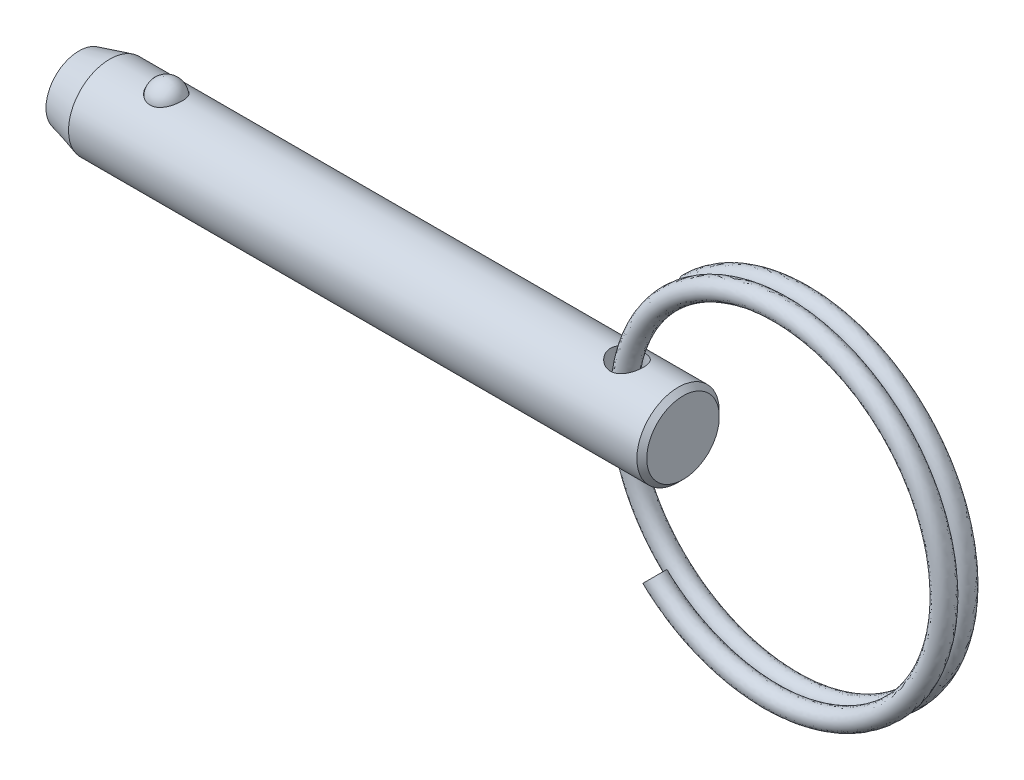
SolidWorks part; units mm, degrees
material "AISI 304"
ref_plane "Front" through (0, 0, 0) normal (0, 0, 1) x (1, 0, 0)
ref_plane "Top" through (0, 0, 0) normal (0, 1, 0) x (1, 0, 0)
ref_plane "Right" through (0, 0, 0) normal (1, 0, 0) x (0, 0, -1)
sketch "Sketch1" plane through (0, 0, 0) normal (0, 0, 1) x (1, 0, 0)
  line L0 (5.588, 2.794) -> (5.207, 3.175)
  line L1 (5.207, 3.175) -> (5.588, 3.175) construction
  line L4 (5.588, 2.794) -> (5.588, 0)
  line L5 (5.588, 3.175) -> (5.588, 2.794) construction
  line L16 (5.207, 3.175) -> (-38.5749, 3.175)
  line L17 (-40.9448, 3.175) -> (-40.9448, 2.54) construction
  line L19 (-38.5749, 3.175) -> (-40.9448, 3.175) construction
  line L22 (-40.9448, -3.175) -> (-38.5749, -3.175) construction
  line L23 (-34.2103, 2.8575) -> (-34.2103, -2.8575) construction
  line L24 (-40.9448, 0) -> (5.588, 0)
  line L27 (5.588, 0) -> (8.382, 0) construction
  line L29 (-40.9448, 0) -> (-40.9448, -2.54) construction
  line L36 (0, 0) -> (0, 3.175) construction
  line L37 (-40.9448, 2.54) -> (-40.9448, 0)
  line L38 (-38.5749, -3.175) -> (5.588, -3.175) construction
  line L39 (-40.9448, -2.54) -> (-40.9448, -3.175) construction
  line L40 (-38.5749, 3.175) -> (-40.9448, 2.54)
  line L42 (-38.5749, -3.175) -> (-40.9448, -2.54) construction
  line L43 (-38.5749, 3.175) -> (-38.5749, -3.175) construction
  circle A2 centre (-34.2103, 2.8575) radius 1.2319 construction
  point P35 (-33.02, 3.175)
  dimension "D2" = 5.715
  dimension "D11" = 0.9144
  dimension "A" = 6.35
  dimension "D" = 5.588
  dimension "E" = 7.2644
  dimension "D3" = 0.381
  dimension "Useable Length" = 33.02
  dimension "D12" = 5.08
  dimension "C" = 7.9248
  dimension "A1" = 15
revolve "Revolve1" add sketch "Sketch1" angle 360 about L27
sketch "Sketch2" plane through (0, 0, 0) normal (0, 0, 1) x (1, 0, 0)
  line L0 (-32.953, 2.8575) -> (-35.4676, 2.8575)
  line L1 (-34.2103, 4.0894) -> (-34.2103, 4.1148) construction
  line L2 (-32.953, 2.8575) -> (-30.4384, 2.8575) construction
  circle A0 centre (-34.2103, 2.8575) radius 1.2319 construction
  circle A1 centre (-34.2103, 2.8575) radius 1.2319 construction
  arc A2 (-35.4676, 2.8575) -> (-32.953, 2.8575) centre (-34.2103, 2.8575) cw
  dimension "D1" = 0.0254
revolve "Cut-Revolve1" cut sketch "Sketch2" angle 360 about L2
sketch "Sketch3" plane through (0, 0, 0) normal (0, 0, 1) x (1, 0, 0)
  line L0 (-32.9784, 2.8575) -> (-35.4422, 2.8575)
  line L1 (-32.9784, 2.8575) -> (-30.5146, 2.8575) construction
  circle A0 centre (-34.2103, 2.8575) radius 1.2319 construction
  arc A1 (-32.9784, 2.8575) -> (-35.4422, 2.8575) centre (-34.2103, 2.8575) ccw
revolve "Revolve2" add sketch "Sketch3" angle 360 about L1
sketch "Sketch4" plane through (0, 0, 0) normal (0, 0, 1) x (1, 0, 0)
  line L1 (1.27, -3.175) -> (2.54, -3.175)
  line L2 (1.27, -3.175) -> (1.27, 3.175)
  line L3 (1.27, 3.175) -> (2.54, 3.175)
  line L4 (2.54, -3.175) -> (2.54, 3.175)
  line L5 (1.27, -3.175) -> (1.27, -4.445) construction
  line L6 (2.54, 3.175) -> (5.588, 3.175) construction
  line L8 (0, -3.175) -> (0, 3.175) construction
  line L9 (0, 0) -> (1.27, 0) construction
  line L11 (1.27, 0) -> (2.54, 0) construction
  line L12 (5.207, 3.175) -> (-38.5749, 3.175) construction
  line L14 (-38.5749, -3.175) -> (5.588, -3.175) construction
  dimension "D1" = 2.54
revolve "Cut-Revolve2" cut sketch "Sketch4" angle 360 about L2
sketch "Sketch5" plane through (0, 0, 0) normal (0, 0, 1) x (1, 0, 0)
  line L0 (0, 0) -> (0.293, 0) construction
  line L1 (0.293, 0) -> (0.293, 3.175) construction
  line L2 (5.207, 3.175) -> (-38.5749, 3.175) construction
  line L3 (13.755, 0) -> (27.217, 0) construction
  line L4 (2.54, 3.175) -> (2.247, 3.175) construction
  line L5 (1.27, 3.175) -> (2.54, 3.175) construction
  line L6 (0.6728, 3.175) -> (0.6728, -3.175) construction
  line L7 (0.293, 3.175) -> (0, 3.175) construction
  line L8 (1.27, -3.175) -> (2.54, -3.175) construction
  line L9 (0.6728, -3.175) -> (2.54, -3.175) construction
  line L10 (0.293, 0) -> (13.755, 0) construction
  line L11 (13.755, 0) -> (8.7098, -10.8195) construction
  line L12 (2.247, 3.175) -> (0.6728, 3.175) construction
  line L13 (13.755, 11.938) -> (13.755, 13.462) construction
  line L14 (8.7098, -10.8195) -> (8.3878, -11.5101) construction
  circle A0 centre (13.755, 0) radius 13.462
  circle A1 centre (13.755, 0) radius 11.938 construction
  circle A2 centre (13.755, 0) radius 12.7 construction
  point P26 (13.755, 12.7)
  dimension "D1" = 65
  dimension "R Ring Dia" = 25.4
  dimension "Ring OD" = 1.524
curve "Helix/Spiral1" pitch 1.5494 height 1.3557 radius 13.462 left hand yes centre (13.755, 0, 0) axis (0, 0, -1) start towards (1, 0, 0)
sketch "Sketch6" plane through (114.0038, 0, 0) normal (0, 1, 0) x (0, 0, -1)
  line L0 (0, 112.1868) -> (0, 112.9488) construction
  line L1 (0, 112.9488) -> (0, 113.7108) construction
  circle A0 centre (0, 112.9488) radius 0.762
  dimension "D1" = 1.524
sketch "Sketch7" plane through (0, 0, 0) normal (0, 0, 1) x (1, 0, 0)
  circle A0 centre (13.755, 0) radius 13.462 construction
  circle A1 centre (13.755, 0) radius 13.462
curve "Helix/Spiral2" pitch 1.5494 height 1.3557 radius 13.462 left hand yes centre (13.755, 0, 0) axis (0, 0, 1) start towards (1, 0, 0)
sweep "Sweep1" add profiles "Sketch6" path "Helix/Spiral1"
sweep "Sweep2" add profiles "Sketch6<2>" path "Helix/Spiral2"
sketch "Sketch6<2>" plane through (114.0038, 0, 0) normal (0, 1, 0) x (0, 0, -1) same geometry as "Sketch6"
ref_plane "Plane1" through (0, -10.8195, 0) normal (0, 1, 0) x (-1, 0, 0)
sketch "Sketch8" plane through (0, -10.8195, 0) normal (0, 1, 0) x (-1, 0, 0)
  line L0 (143.6902, 0) -> (-8.7098, 0) construction
  line L1 (10.3402, -0.7779) -> (4.5066, -0.7779)
  line L2 (3.5004, -0.9415) -> (-7.2005, -4.517)
  line L3 (-7.2005, 4.517) -> (3.5004, 0.9415)
  line L4 (4.5066, 0.7779) -> (130.4738, 0.7779)
  line L5 (131.48, 0.9415) -> (142.1809, 4.517)
  line L6 (124.6402, -0.7779) -> (130.4738, -0.7779)
  line L7 (131.48, -0.9415) -> (142.1809, -4.517)
  line L8 (10.3402, -0.7779) -> (10.3402, 0.7779) construction
  arc A0 (-7.2005, 4.517) -> (-7.2005, -4.517) centre (-8.7098, 0) ccw
  arc A1 (142.1809, -4.517) -> (142.1809, 4.517) centre (143.6902, 0) ccw
  arc A2 (4.5066, -0.7779) -> (3.5004, -0.9415) centre (4.5066, -3.9529) ccw
  arc A3 (3.5004, 0.9415) -> (4.5066, 0.7779) centre (4.5066, 3.9529) ccw
  arc A4 (130.4738, -0.7779) -> (131.48, -0.9415) centre (130.4738, -3.9529) cw
  arc A5 (130.4738, 0.7779) -> (131.48, 0.9415) centre (130.4738, 3.9529) ccw
  point P6 (10.3402, 0)
  point P16 (3.9902, -0.7779)
  point P20 (3.9902, 0.7779)
  point P23 (130.9902, -0.7779)
  point P26 (130.9902, 0.7779)
  dimension "D2" = 4.7625
  dimension "D3" = 1.5557
  dimension "D6" = 3.175
  dimension "Lanyard Length" = 152.4
  dimension "D4" = 6.35
  dimension "D5" = 12.7
ref_plane "Plane2" through (-10.3402, 0, 0) normal (1, 0, 0) x (0, 0, -1)
sketch "Sketch9" plane through (-10.3402, 0, 0) normal (1, 0, 0) x (0, 0, -1)
  circle A0 centre (0.7779, -10.8195) radius 0.7779
sweep "Sweep3" [suppressed] add profiles "Sketch9" path "Sketch8"
sketch "Sketch10" [suppressed] plane through (-10.3402, 0, 0) normal (1, 0, 0) x (0, 0, -1)
  arc A0 (-0.3849, -10.1482) -> (-0.3849, -11.4908) centre (-0.7779, -10.8195) ccw
  circle A1 centre (0.7779, -10.8195) radius 0.7779
  arc A2 (0.3849, -11.4908) -> (0.3849, -10.1482) centre (0.7779, -10.8195) ccw
  arc A3 (-0.3849, -11.4908) -> (0.3849, -11.4908) centre (0, -12.1485) cw
  arc A4 (-0.3869, -9.3301) -> (-0.3869, -12.3089) centre (-0.7779, -10.8195) ccw
  arc A5 (0.3869, -12.3089) -> (0.3869, -9.3301) centre (0.7779, -10.8195) ccw
  circle A6 centre (-0.7779, -10.8195) radius 1.5399 construction
  circle A7 centre (-0.7779, -10.8195) radius 0.7779 construction
  arc A8 (-0.3849, -10.1482) -> (0.3849, -10.1482) centre (0, -9.4905) ccw
  arc A9 (-0.3869, -9.3301) -> (0.3869, -9.3301) centre (0, -7.856) ccw
  arc A10 (0.3869, -12.3089) -> (-0.3869, -12.3089) centre (0, -13.783) ccw
  point P4 (-0.034, -10.2746)
  point P8 (2.3178, -10.502)
  point P9 (0.762, -10.502)
  dimension "D3" = 1.524
  dimension "D4" = 0.762
  dimension "D2" = 0.762
  dimension "D1" = 0
extrude "Extrude1" [suppressed] add sketch "Sketch10" along normal blind 5.715 separate body
sketch "Sketch11" [suppressed] plane through (-124.6402, 0, 0) normal (1, 0, 0) x (0, 0, -1)
  arc A4 (-0.3849, -10.1482) -> (-0.3849, -11.4908) centre (-0.7779, -10.8195) ccw
  arc A5 (0.3849, -11.4908) -> (-0.3849, -11.4908) centre (0, -12.1485) ccw
  arc A6 (0.3849, -11.4908) -> (0.3849, -10.1482) centre (0.7779, -10.8195) ccw
  arc A7 (-0.3849, -10.1482) -> (0.3849, -10.1482) centre (0, -9.4905) ccw
  arc A8 (-0.3849, -10.1482) -> (-0.3849, -11.4908) centre (-0.7779, -10.8195) ccw
  arc A9 (0.3849, -11.4908) -> (-0.3849, -11.4908) centre (0, -12.1485) ccw
  arc A10 (0.3849, -11.4908) -> (0.3849, -10.1482) centre (0.7779, -10.8195) ccw
  arc A11 (-0.3849, -10.1482) -> (0.3849, -10.1482) centre (0, -9.4905) ccw
  arc A12 (-0.3869, -9.3301) -> (-0.3869, -12.3089) centre (-0.7779, -10.8195) ccw
  arc A13 (0.3869, -12.3089) -> (-0.3869, -12.3089) centre (0, -13.783) ccw
  arc A14 (0.3869, -12.3089) -> (0.3869, -9.3301) centre (0.7779, -10.8195) ccw
  arc A15 (-0.3869, -9.3301) -> (0.3869, -9.3301) centre (0, -7.856) ccw
  arc A16 (-0.3869, -9.3301) -> (-0.3869, -12.3089) centre (-0.7779, -10.8195) ccw
  arc A17 (0.3869, -12.3089) -> (-0.3869, -12.3089) centre (0, -13.783) ccw
  arc A18 (0.3869, -12.3089) -> (0.3869, -9.3301) centre (0.7779, -10.8195) ccw
  arc A19 (-0.3869, -9.3301) -> (0.3869, -9.3301) centre (0, -7.856) ccw
  dimension "D1" = 0
  dimension "D2" = 0
extrude "Extrude2" [suppressed] add sketch "Sketch11" against normal blind 5.715 separate body
sketch "Sketch12" plane through (0, -10.8195, 0) normal (0, 1, 0) x (-1, 0, 0)
  line L0 (174.4712, -5.2864) -> (168.9086, -5.2864) construction
  line L1 (174.4712, -5.9214) -> (158.1026, -5.9214)
  line L2 (174.4712, -5.9214) -> (174.4712, -4.6514)
  line L3 (174.4712, -4.6514) -> (158.3265, -4.6514)
  line L4 (158.1026, -5.9214) -> (158.3265, -4.6514) construction
  line L5 (158.1026, -5.9214) -> (142.7212, -0.3231)
  line L6 (168.9086, -5.2864) -> (158.2146, -5.2864) construction
  line L7 (158.3265, -4.6514) -> (143.1555, 0.8704)
  line L8 (142.7212, -0.3231) -> (143.1555, 0.8704)
  line L9 (158.2146, -5.2864) -> (148.1655, -1.6289) construction
  line L10 (148.1655, -1.6289) -> (142.9383, 0.2737) construction
  arc A0 (142.1809, -4.517) -> (142.1809, 4.517) centre (143.6902, 0) ccw construction
  dimension "D1" = 20
  dimension "D2" = 31.75
  dimension "D3" = 1.27
  dimension "D4" = 5.5626
extrude "Extrude3" [suppressed] add sketch "Sketch12" along normal mid plane 12.7 separate body
sketch "Sketch13" [suppressed] plane through (0, 0, -4.6514) normal (0, 0, 1) x (1, 0, 0)
  line L0 (-174.4712, -10.8195) -> (-158.3265, -10.8195) construction
  line L1 (-172.4782, -4.4695) -> (-174.4712, -4.4695)
  line L2 (-174.4712, -4.4695) -> (-158.3265, -4.4695) construction
  line L3 (-174.4712, -4.4695) -> (-176.4642, -4.4695)
  line L4 (-176.4642, -4.4695) -> (-176.4642, -17.1695)
  line L5 (-176.4642, -17.1695) -> (-174.4712, -17.1695)
  line L6 (-174.4712, -17.1695) -> (-172.4782, -17.1695)
  line L7 (-174.4712, -17.1695) -> (-158.3265, -17.1695) construction
  arc A0 (-172.4782, -4.4695) -> (-172.4782, -17.1695) centre (-163.3587, -10.8195) ccw
  circle A1 centre (-168.9086, -10.8195) radius 2.5781
  dimension "D1" = 5.1562
  dimension "D2" = 11.1125
extrude "Extrude4" [suppressed] cut sketch "Sketch13" against normal up to surface (1.27 mm away)
sketch "Sketch14" [suppressed] plane through (-17.0257, 0, 46.7778) normal (-0.342, 0, 0.9397) x (0.9397, 0, 0.342)
  line L3 (-136.2175, -4.4695) -> (-134.2245, -4.4695)
  line L4 (-134.2245, -4.4695) -> (-132.2315, -4.4695)
  line L5 (-132.2315, -4.4695) -> (-132.2315, -17.1695)
  line L6 (-132.2315, -17.1695) -> (-134.2245, -17.1695)
  line L7 (-134.2245, -17.1695) -> (-136.2175, -17.1695)
  line L8 (-134.2245, -4.4695) -> (-134.2245, -17.1695) construction
  line L9 (-150.3692, -4.4695) -> (-134.2245, -4.4695) construction
  line L10 (-150.4811, -10.8195) -> (-139.7871, -10.8195) construction
  arc A0 (-136.2175, -17.1695) -> (-136.2175, -4.4695) centre (-145.337, -10.8195) ccw
  circle A1 centre (-139.7871, -10.8195) radius 2.5781
  dimension "D1" = 5.1562
  dimension "D2" = 11.1125
extrude "Extrude6" [suppressed] cut sketch "Sketch14" against normal up to surface (1.27 mm away)
sketch "Sketch15" [suppressed] plane through (0, 0, 0) normal (0, 0, 1) x (1, 0, 0)
  line L1 (-258.031, -4.4695) -> (-99.281, -4.4695)
  line L2 (-258.031, -4.4695) -> (-270.731, -17.1695)
  line L3 (-270.731, -17.1695) -> (-111.981, -17.1695)
  line L4 (-99.281, -4.4695) -> (-111.981, -17.1695)
  line L5 (-325.1006, -4.4695) -> (-310.949, -4.4695) construction
  line L6 (-325.1006, -17.1695) -> (-310.949, -17.1695) construction
  circle A0 centre (-321.531, -10.8195) radius 2.5781 construction
  dimension "D1" = 63.5
  dimension "D2" = 158.75
  dimension "D3" = 45
extrude "Extrude7" [suppressed] cut sketch "Sketch15" against normal through all and the other way through all
move or copy body "Body-Move/Copy1" [suppressed] bodies to move or copy 147 151 144 copy no translate (152.4, 0, 0)
sketch "Sketch16" [suppressed] plane through (0, 0, 0) normal (0, 0, 1) x (1, 0, 0)
  line L0 (-111.981, -6.057) -> (-111.981, -9.232) construction
  line L1 (-111.981, -9.232) -> (-109.441, -8.2795) construction
  line L2 (-109.441, -8.2795) -> (-114.521, -13.3595) construction
  line L3 (-114.521, -13.3595) -> (-111.981, -12.407) construction
  line L4 (-111.981, -12.407) -> (-111.981, -15.582) construction
  line L5 (-112.7589, -11.5974) -> (-111.2032, -10.0416) construction
  line L6 (-105.631, -15.582) -> (-105.631, -12.407) construction
  line L7 (-105.631, -12.407) -> (-108.171, -13.3595) construction
  line L8 (-108.171, -13.3595) -> (-103.091, -8.2795) construction
  line L9 (-103.091, -8.2795) -> (-105.631, -9.232) construction
  line L10 (-105.631, -9.232) -> (-105.631, -6.057) construction
  line L11 (-104.8532, -10.0416) -> (-106.4089, -11.5974) construction
  line L14 (-4.7291, -10.8195) -> (-283.0963, -10.8195) construction
  dimension "D1" = 3.175
  dimension "D2" = 3.175
  dimension "D3" = 5.08
  dimension "D4" = 1.5875
equation "\"D12@Sketch1\"=\"A@Sketch1\" * 0.80"
equation "\"D2@Sketch1\"=\"A@Sketch1\" * 0.9"
equation "\"D1@Sketch4\" = \"A@Sketch1\" / 2.5"
equation "\"Ring OD@Sketch5\" = \"R Ring Dia@Sketch5\" * 0.06"
equation "\"D4@Helix/Spiral1\"=\"Ring OD@Sketch5\" + 0.001"
equation "\"D1@Sketch6\"=\"Ring OD@Sketch5\""
equation "\"D4@Helix/Spiral2\" = \"D4@Helix/Spiral1\""
equation "\"D5@Helix/Spiral2\" = \"D5@Helix/Spiral1\""
equation "\"D1@Sketch14\" = \"D1@Sketch13\""
equation "\"D2@Sketch14\" = \"D2@Sketch13\""
